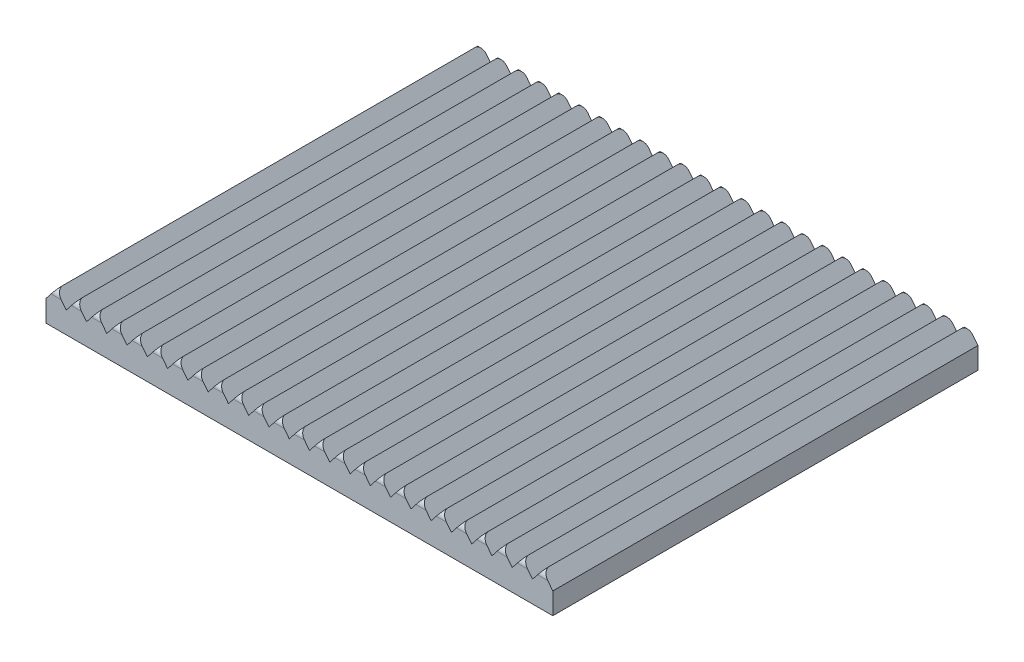
SolidWorks part; units mm, degrees
ref_plane "Front Plane" through (0, 0, 0) normal (0, 0, 1) x (1, 0, 0)
ref_plane "Top Plane" through (0, 0, 0) normal (0, 1, 0) x (1, 0, 0)
ref_plane "Right Plane" through (0, 0, 0) normal (1, 0, 0) x (0, 0, -1)
sketch "Sketch1" plane through (0, 0, 0) normal (0, 1, 0) x (1, 0, 0)
  line L6 (-29.5, 24.75) -> (29.5, 24.75)
  line L28 (-29.5, 24.75) -> (-29.5, -24.75)
  line L29 (-29.5, -24.75) -> (29.5, -24.75)
  line L30 (29.5, 24.75) -> (29.5, -24.75)
  line L31 (-29.5, 24.75) -> (29.5, -24.75) construction
  line L32 (-29.5, -24.75) -> (29.5, 24.75) construction
  circle A1 centre (0, 0) radius 3
  point P0 (0, 0)
  dimension "D3" = 6
  dimension "D1" = 59
  dimension "D2" = 49.5
extrude "Boss-Extrude1" add sketch "Sketch1" along normal blind 1.5
sketch "Sketch2" plane through (0, 0, -24.75) normal (0, 0, -1) x (-1, 0, 0)
  line L0 (-29.5, 1.5) -> (-29.5, 0) construction
  line L1 (-29.5, 1.5) -> (29.5, 1.5)
  line L2 (-29.5, 1.5) -> (-29.5, 2.5)
  line L4 (29.5, 1.5) -> (29.5, 2.5)
  line L5 (-1.18, 2.5) -> (0, 4)
  line L6 (0, 55) -> (0, -55) construction
  line L7 (1.18, 2.5) -> (0, 4)
  line L8 (1.18, 2.5) -> (2.36, 4)
  line L9 (3.54, 2.5) -> (2.36, 4)
  line L10 (3.54, 2.5) -> (4.72, 4)
  line L11 (5.9, 2.5) -> (4.72, 4)
  line L12 (5.9, 2.5) -> (7.08, 4)
  line L13 (8.26, 2.5) -> (7.08, 4)
  line L14 (8.26, 2.5) -> (9.44, 4)
  line L15 (10.62, 2.5) -> (9.44, 4)
  line L16 (10.62, 2.5) -> (11.8, 4)
  line L17 (12.98, 2.5) -> (11.8, 4)
  line L18 (12.98, 2.5) -> (14.16, 4)
  line L19 (15.34, 2.5) -> (14.16, 4)
  line L20 (15.34, 2.5) -> (16.52, 4)
  line L21 (17.7, 2.5) -> (16.52, 4)
  line L22 (17.7, 2.5) -> (18.88, 4)
  line L23 (20.06, 2.5) -> (18.88, 4)
  line L24 (20.06, 2.5) -> (21.24, 4)
  line L25 (22.42, 2.5) -> (21.24, 4)
  line L26 (22.42, 2.5) -> (23.6, 4)
  line L27 (24.78, 2.5) -> (23.6, 4)
  line L28 (24.78, 2.5) -> (25.96, 4)
  line L29 (27.14, 2.5) -> (25.96, 4)
  line L30 (27.14, 2.5) -> (28.32, 4)
  line L31 (29.5, 2.5) -> (28.32, 4)
  line L32 (-29.5, 2.5) -> (-28.32, 4)
  line L33 (-27.14, 2.5) -> (-28.32, 4)
  line L34 (-27.14, 2.5) -> (-25.96, 4)
  line L35 (-24.78, 2.5) -> (-25.96, 4)
  line L36 (-24.78, 2.5) -> (-23.6, 4)
  line L37 (-22.42, 2.5) -> (-23.6, 4)
  line L38 (-22.42, 2.5) -> (-21.24, 4)
  line L39 (-20.06, 2.5) -> (-21.24, 4)
  line L40 (-20.06, 2.5) -> (-18.88, 4)
  line L41 (-17.7, 2.5) -> (-18.88, 4)
  line L42 (-17.7, 2.5) -> (-16.52, 4)
  line L43 (-15.34, 2.5) -> (-16.52, 4)
  line L44 (-15.34, 2.5) -> (-14.16, 4)
  line L45 (-12.98, 2.5) -> (-14.16, 4)
  line L46 (-12.98, 2.5) -> (-11.8, 4)
  line L47 (-10.62, 2.5) -> (-11.8, 4)
  line L48 (-10.62, 2.5) -> (-9.44, 4)
  line L49 (-8.26, 2.5) -> (-9.44, 4)
  line L50 (-8.26, 2.5) -> (-7.08, 4)
  line L51 (-5.9, 2.5) -> (-7.08, 4)
  line L52 (-5.9, 2.5) -> (-4.72, 4)
  line L53 (-3.54, 2.5) -> (-4.72, 4)
  line L54 (-3.54, 2.5) -> (-2.36, 4)
  line L55 (-1.18, 2.5) -> (-2.36, 4)
  dimension "D1" = 1
  dimension "D2" = 1.5
  dimension "D3" = 13
extrude "Boss-Extrude2" add sketch "Sketch2" against normal up to surface (49.5 mm away) up to face at (0, 0.75, 24.75)
sketch "Sketch3" plane through (0, 0, 0) normal (0, -1, 0) x (-1, 0, 0)
  line L0 (0, 55) -> (0, -55) construction
  line L2 (-1.75, -2.4367) -> (-1.75, -5)
  line L3 (-1.75, -5) -> (1.75, -5)
  line L4 (1.75, -2.4367) -> (1.75, -5)
  arc A0 (1.75, -2.4367) -> (-1.75, -2.4367) centre (0, 0) ccw
  dimension "D2" = 6
  dimension "D1" = 3.5
  dimension "D3" = 5
  dimension "D4" = 1.75
extrude "Cut-Extrude1" cut sketch "Sketch3" against normal blind 1
sketch "Sketch4" plane through (29.5, 0, 0) normal (1, 0, 0) x (0, 0, -1)
  line L1 (-24.75, 4) -> (-24.75, 2.5) construction
  line L2 (-24.75, 4) -> (24.75, 4) construction
  line L3 (-24, 4) -> (-24.75, 4)
  line L4 (-24.75, 4) -> (-24.75, 3.25)
  arc A0 (-24.75, 3.25) -> (-24, 4) centre (-24, 3.25) cw
extrude "Cut-Extrude3" cut sketch "Sketch4" against normal through all
mirror "Mirror1" about plane through (0, 0, 0) normal (0, 0, 1) of "Cut-Extrude3"
sketch "Sketch5" plane through (0, 1.5, 0) normal (0, -1, 0) x (1, 0, 0)
  circle A0 centre (0, 0) radius 3
  dimension "D1" = 6
extrude "Boss-Extrude3" add sketch "Sketch5" along normal blind 0.5
sketch "Sketch6" plane through (0, 1, 0) normal (0, -1, 0) x (1, 0, 0)
  line L1 (1.75, 5) -> (-1.75, 5)
  line L2 (1.75, 5) -> (1.75, 2.4367)
  line L3 (1.75, 2.4367) -> (-1.75, 2.4367)
  line L4 (-1.75, 5) -> (-1.75, 2.4367)
extrude "Cut-Extrude4" cut sketch "Sketch6" against normal blind 0.5
chamfer "Chamfer3" distance 1.5 angle 45 1 edges at (0, 0, 5)
